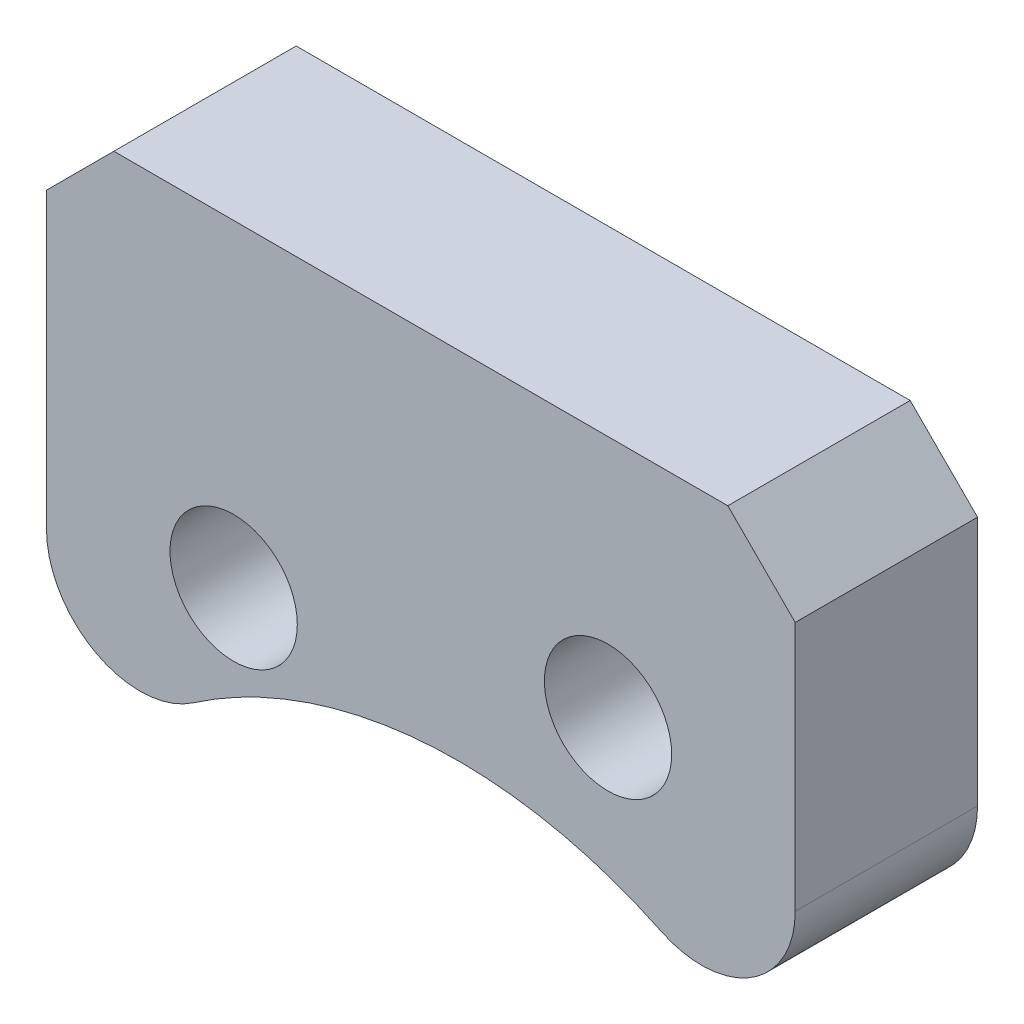
SolidWorks part; units mm, degrees
ref_plane "Front Plane" through (0, 0, 0) normal (0, 0, 1) x (1, 0, 0)
ref_plane "Top Plane" through (0, 0, 0) normal (0, 1, 0) x (1, 0, 0)
ref_plane "Right Plane" through (0, 0, 0) normal (1, 0, 0) x (0, 0, -1)
sketch "Sketch1" plane through (0, 0, 0) normal (0, 0, 1) x (1, 0, 0)
  line L0 (-20, 0) -> (0, 0)
  line L2 (-20, -16.0628) -> (-20, 0)
  line L4 (0, -13.3253) -> (0, 0)
  arc A0 (0, -13.3253) -> (-20, -16.0628) centre (-9, -22) ccw
  circle A1 centre (-15, -8.5) radius 1.7
  circle A2 centre (-5, -6.5) radius 1.7
  dimension "D4" = 22
  dimension "10.5" = 12.5
  dimension "D2" = 3.4
  dimension "D1" = 9
  dimension "D3" = 20
  dimension "D5" = 5
  dimension "D6" = 15
  dimension "D7" = 6.5
  dimension "D8" = 8.5
extrude "Boss-Extrude1" add sketch "Sketch1" along normal blind 4.87
chamfer "Chamfer1" distance 1.8 angle 45 2 edges at (0, 0, 2.435) (-20, 0, 2.435)
fillet "Fillet1" radius 2.5 2 edges at (0, -13.3253, 2.435) (-20, -16.0628, 2.435)
